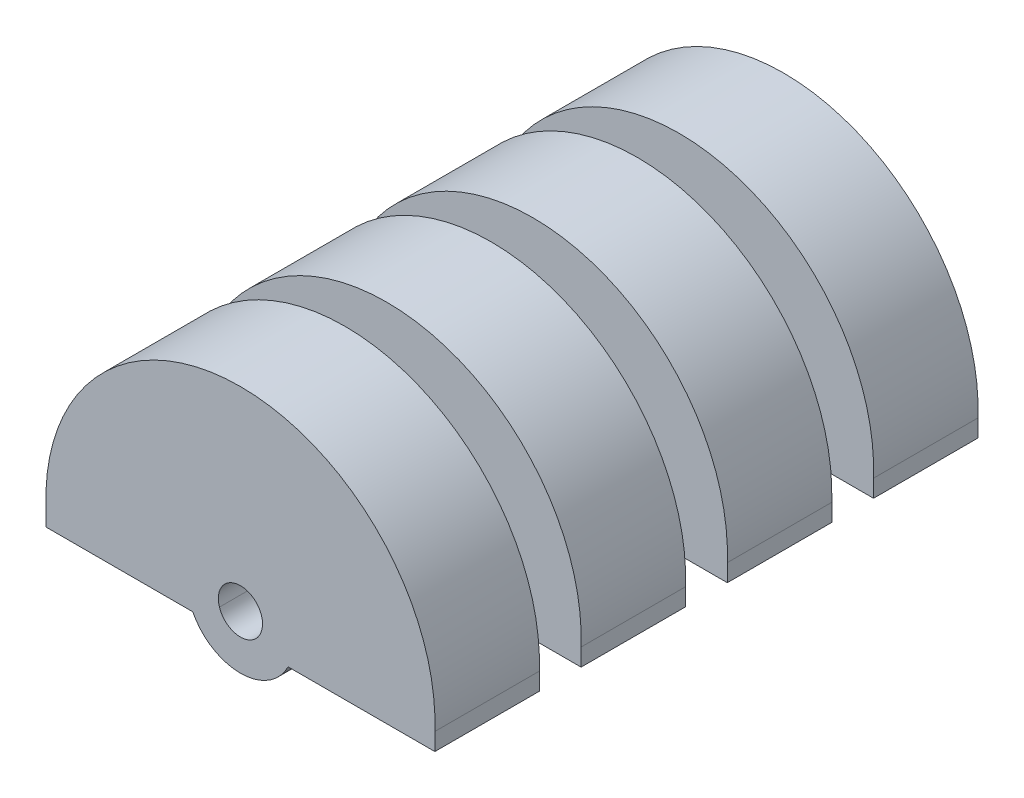
SolidWorks part; units mm, degrees
material "RUBBER 65A Test Modulus"
ref_plane "Front Plane" through (0, 0, 0) normal (0, 0, 1) x (1, 0, 0)
ref_plane "Top Plane" through (0, 0, 0) normal (0, 1, 0) x (1, 0, 0)
ref_plane "Right Plane" through (0, 0, 0) normal (1, 0, 0) x (0, 0, -1)
sketch "Sketch3" plane through (0, 0, 0) normal (0, 0, 1) x (1, 0, 0)
  circle A0 centre (0, 0) radius 27.94
  dimension "D1" = 55.88
extrude "Boss-Extrude2" add sketch "Sketch3" along normal blind 78
ref_axis "Axis2" through (0, 0, 77.1287) along (0, 0, -1)
sketch "Sketch5" plane through (0, 0, 78) normal (0, 0, 1) x (1, 0, 0)
  circle A0 centre (0, 0) radius 3.175
  dimension "D1" = 6.35
extrude "Cut-Extrude1" cut sketch "Sketch5" against normal through all contours A0
sketch "Sketch4" plane through (0, 0, 0) normal (0, 1, 0) x (1, 0, 0)
  line L0 (0, -78) -> (0, 0) construction
  line L1 (-27.94, -78) -> (27.94, -78) construction
  line L3 (-27.94, -63) -> (-13.94, -63)
  line L4 (-27.94, -63) -> (-27.94, -57)
  line L5 (-27.94, -57) -> (-13.94, -57)
  line L6 (-13.94, -63) -> (-13.94, -57)
  line L63 (-27.94, -42) -> (-27.94, -36)
  line L64 (-27.94, -42) -> (-13.94, -42)
  line L65 (-13.94, -42) -> (-13.94, -36)
  line L66 (-27.94, -36) -> (-13.94, -36)
  line L67 (-27.94, -21) -> (-27.94, -15)
  line L68 (-27.94, -21) -> (-13.94, -21)
  line L69 (-13.94, -21) -> (-13.94, -15)
  line L70 (-27.94, -15) -> (-13.94, -15)
  line L91 (-27.94, -63) -> (-27.94, -42) construction
  line L92 (-27.94, 42) -> (-27.94, 48) [skipped]
  line L93 (-27.94, 42) -> (-13.94, 42) [skipped]
  line L94 (-13.94, 42) -> (-13.94, 48) [skipped]
  line L95 (-27.94, 48) -> (-13.94, 48) [skipped]
  line L96 (-27.94, 63) -> (-27.94, 69) [skipped]
  line L97 (-27.94, 63) -> (-13.94, 63) [skipped]
  line L98 (-13.94, 63) -> (-13.94, 69) [skipped]
  line L99 (-27.94, 69) -> (-13.94, 69) [skipped]
  line L100 (-27.94, 84) -> (-27.94, 90) [skipped]
  line L101 (-27.94, 84) -> (-13.94, 84) [skipped]
  line L102 (-13.94, 84) -> (-13.94, 90) [skipped]
  line L103 (-27.94, 90) -> (-13.94, 90) [skipped]
  line L105 (-27.94, 21) -> (-27.94, 27) [skipped]
  line L106 (-27.94, 27) -> (-13.94, 27) [skipped]
  line L107 (-13.94, 21) -> (-13.94, 27) [skipped]
  line L108 (-27.94, 21) -> (-13.94, 21) [skipped]
  line L109 (-27.94, 0) -> (-27.94, 6) [skipped]
  line L110 (-27.94, 6) -> (-13.94, 6) [skipped]
  line L111 (-13.94, 0) -> (-13.94, 6) [skipped]
  line L112 (-27.94, 0) -> (-13.94, 0) [skipped]
  dimension "D1" = 15
  dimension "D2" = 6
  dimension "D3" = 27.94
  dimension "D4" = 14
  dimension "D6" = 21
  dimension "D5" = 8
revolve "Cut-Revolve1" cut sketch "Sketch4" angle 360 about L0
shell "Shell1" thickness 4.5
sketch "Sketch10" plane through (0, 0, 0) normal (0, 0, -1) x (-1, 0, 0)
  line L0 (0, 27.94) -> (0, -27.94) construction
  line L1 (-27.94, 0) -> (27.94, 0) construction
  line L2 (-1, 27.9221) -> (-1, 3.0134)
  line L3 (1, 3.0134) -> (1, 27.9221)
  line L4 (3.0134, 1) -> (27.9221, 1)
  line L5 (3.0134, -1) -> (27.9221, -1)
  line L6 (-1, -3.0134) -> (-1, -27.9221)
  line L7 (1, -3.0134) -> (1, -27.9221)
  line L8 (-27.9221, -1) -> (-3.0134, -1)
  line L9 (-27.9221, 1) -> (-3.0134, 1)
  circle A0 centre (0, 0) radius 27.94 construction
  circle A1 centre (0, 0) radius 3.175 construction
  arc A2 (-1, -27.9221) -> (1, -27.9221) centre (0, 0) ccw
  arc A3 (27.9221, -1) -> (27.9221, 1) centre (0, 0) ccw
  arc A4 (1, 27.9221) -> (-1, 27.9221) centre (0, 0) ccw
  arc A5 (-27.9221, 1) -> (-27.9221, -1) centre (0, 0) ccw
  arc A6 (-1, -3.0134) -> (1, -3.0134) centre (0, 0) ccw
  arc A7 (-3.0134, 1) -> (-3.0134, -1) centre (0, 0) ccw
  arc A8 (1, 3.0134) -> (-1, 3.0134) centre (0, 0) ccw
  arc A9 (3.0134, -1) -> (3.0134, 1) centre (0, 0) ccw
  dimension "D1" = 1
  dimension "D2" = 1
  dimension "D3" = 1
  dimension "D4" = 1
  dimension "D5" = 1
extrude "Boss-Extrude3" add sketch "Sketch10" against normal up to surface (78 mm away) up to face at (3.175, 0, 78)
sketch "Sketch16" plane through (0, 0, 0) normal (0, 0, -1) x (-1, 0, 0)
  line L0 (27.94, 0) -> (-27.94, 0) construction
  line L1 (0, 0) -> (0, -1) construction
  line L2 (27.9221, -1) -> (-27.9221, -1) construction
  line L3 (-3.0134, -1) -> (-27.9221, -1)
  line L4 (27.9221, -1) -> (3.0134, -1)
  arc A2 (-27.9221, -1) -> (27.9221, -1) centre (0, 0) ccw
  circle A4 centre (0, 0) radius 27.94 construction
  arc A5 (-3.0134, -1) -> (3.0134, -1) centre (0, 0) ccw
  circle A6 centre (0, 0) radius 3.175 construction
  point P5 (0, 0)
  point P10 (0, -1)
extrude "Cut-Extrude3" cut sketch "Sketch16" against normal blind 78
sketch "Sketch18" plane through (0, 0, 0) normal (0, 0, -1) x (-1, 0, 0)
  line L2 (-6.0982, -0.971) -> (-27.9231, -0.971) construction
  line L3 (0, 0) -> (0, -1) construction
  line L4 (27.9221, -1) -> (-27.9221, -1) construction
  line L5 (3.0134, -1) -> (27.9221, -1) construction
  line L6 (-3.0134, -1) -> (-27.9221, -1)
  line L7 (3.0134, -1) -> (27.9221, -1)
  line L8 (-27.9221, -1) -> (-27.9221, -3.5)
  line L9 (27.9221, -1) -> (27.8863, -3.4994)
  line L10 (-27.9221, -3.5) -> (27.8863, -3.4994) construction
  line L11 (0, -3.217) -> (0, -7.717) construction
  line L12 (-27.9221, -3.5) -> (-6.8404, -3.5)
  line L13 (27.8863, -3.4994) -> (6.8406, -3.4996)
  arc A3 (-3.0134, -1) -> (3.0134, -1) centre (0, -0.0606) ccw
  arc A5 (-6.8404, -3.5) -> (6.8406, -3.4996) centre (0, -0.0606) ccw
  point P6 (0, -1)
extrude "Boss-Extrude5" add sketch "Sketch18" against normal blind 78
sketch "Sketch13" plane through (0, 0, 0) normal (0, 1, 0) x (1, 0, 0)
  line L0 (-30.3872, -36) -> (-13.9041, -36)
  line L1 (-30.3872, -15) -> (-13.9041, -15)
  line L2 (-30.3872, -15) -> (-30.3872, -21)
  line L3 (-30.3872, -21) -> (-13.9041, -21)
  line L4 (-13.9041, -15) -> (-13.9041, -21)
  line L5 (-30.3872, -36) -> (-30.3872, -42)
  line L6 (-30.3872, -42) -> (-13.9041, -42)
  line L7 (-13.9041, -36) -> (-13.9041, -42)
  line L8 (-30.3872, -57) -> (-13.9041, -57)
  line L9 (-30.3872, -57) -> (-30.3872, -63)
  line L10 (-30.3872, -63) -> (-13.9041, -63)
  line L11 (-13.9041, -57) -> (-13.9041, -63)
  line L20 (-30.3872, -78) -> (-13.9041, -78) [skipped]
  line L21 (-13.9041, -78) -> (-13.9041, -84) [skipped]
  line L22 (-30.3872, -84) -> (-13.9041, -84) [skipped]
  line L23 (-30.3872, -78) -> (-30.3872, -84) [skipped]
  line L24 (-30.3872, -99) -> (-13.9041, -99) [skipped]
  line L25 (-13.9041, -99) -> (-13.9041, -105) [skipped]
  line L26 (-30.3872, -105) -> (-13.9041, -105) [skipped]
  line L27 (-30.3872, -99) -> (-30.3872, -105) [skipped]
  dimension "D2" = 6
  dimension "D1" = 5
revolve "Cut-Revolve2" cut sketch "Sketch13" angle 360 about axis through (0, 0, 77.1287) along (0, 0, -1)
equation "\"inwall\"= .75"
equation "\"outwall\"=2"
